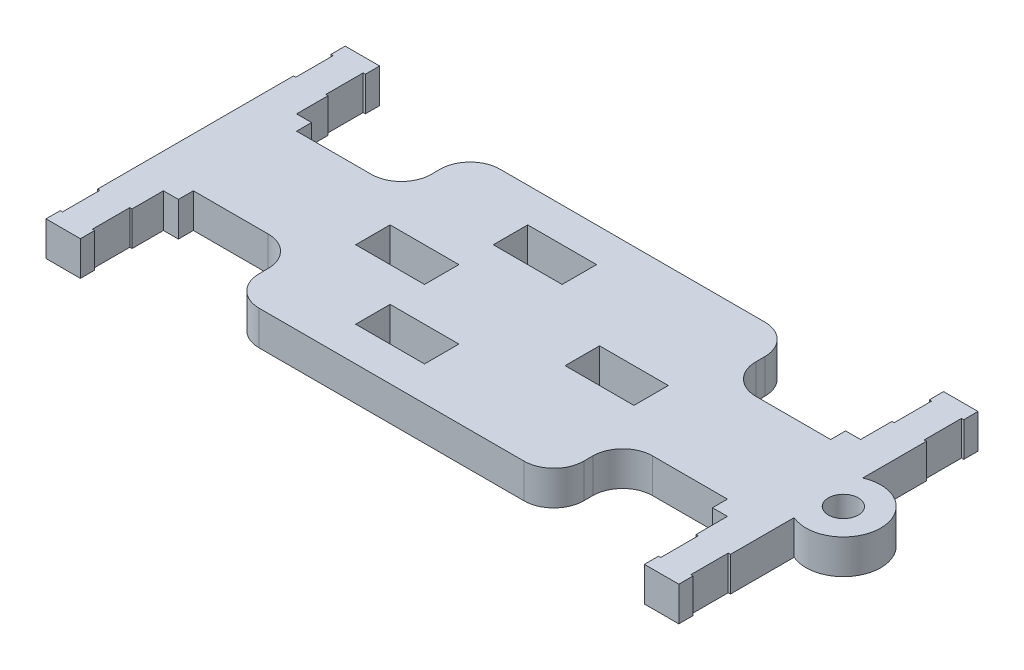
SolidWorks part; units mm, degrees
ref_plane "Front Plane" through (0, 0, 0) normal (0, 0, 1) x (1, 0, 0)
ref_plane "Top Plane" through (0, 0, 0) normal (0, 1, 0) x (1, 0, 0)
ref_plane "Right Plane" through (0, 0, 0) normal (1, 0, 0) x (0, 0, -1)
sketch "Sketch1" plane through (0, 0, 0) normal (0, 1, 0) x (1, 0, 0)
  line L0 (-15.3614, 0) -> (15.3614, 0) construction
  line L1 (-21.15, -10) -> (21.15, -10)
  line L2 (-21.15, -10) -> (-21.15, 10)
  line L3 (-21.15, 10) -> (21.15, 10)
  line L4 (21.15, -10) -> (21.15, 10)
  line L5 (-21.15, -10) -> (21.15, 10) construction
  line L6 (-21.15, 10) -> (21.15, -10) construction
  line L7 (-4.7, -1.15) -> (-9.3, -1.15)
  line L8 (-4.7, -1.15) -> (-4.7, 1.15)
  line L9 (-4.7, 1.15) -> (-9.3, 1.15)
  line L10 (-9.3, -1.15) -> (-9.3, 1.15)
  line L11 (-4.7, -1.15) -> (-9.3, 1.15) construction
  line L12 (-4.7, 1.15) -> (-9.3, -1.15) construction
  line L13 (-4.7, -3.45) -> (-0.1, -3.45)
  line L14 (-4.7, -3.45) -> (-4.7, -5.75)
  line L15 (-4.7, -5.75) -> (-0.1, -5.75)
  line L16 (-0.1, -3.45) -> (-0.1, -5.75)
  line L17 (0, -4.6731) -> (0, 4.6731) construction
  line L18 (9.3, -1.15) -> (9.3, 1.15)
  line L19 (4.7, 1.15) -> (9.3, 1.15)
  line L20 (4.7, -1.15) -> (9.3, -1.15)
  line L21 (4.7, -1.15) -> (4.7, 1.15)
  line L22 (-4.7, 5.75) -> (-0.1, 5.75)
  line L23 (-0.1, 3.45) -> (-0.1, 5.75)
  line L24 (-4.7, 3.45) -> (-0.1, 3.45)
  line L25 (-4.7, 3.45) -> (-4.7, 5.75)
  point P0 (0, 0)
  point P6 (-7, 0)
  point P19 (0, 0)
  point P21 (0, 0)
  dimension "D1" = 20
  dimension "D2" = 42.3
  dimension "D3" = 4.7
  dimension "D4" = 4.6
  dimension "D5" = 2.3
  dimension "D6" = 4.6
  dimension "D7" = 2.3
  dimension "D8" = 2.3
base flange "Base-Flange1" sketch "Sketch1" thickness 2.3 reverse thickness direction no parameters "D1"=0.7366
sketch "Sketch6" plane through (0, 0, 0) normal (0, 1, 0) x (1, 0, 0)
  line L0 (-2.4727, 0) -> (2.4727, 0) construction
  line L1 (-18.85, 10) -> (-18.85, 4.45)
  line L2 (21.15, 10) -> (-21.15, 10) construction
  line L3 (-17.85, 3.45) -> (-12.85, 3.45)
  line L4 (-10.85, 5.45) -> (-10.85, 6.05)
  line L5 (-8.85, 8.05) -> (8.85, 8.05)
  line L6 (10.85, 6.05) -> (10.85, 5.45)
  line L7 (12.85, 3.45) -> (17.85, 3.45)
  line L8 (18.85, 4.45) -> (18.85, 10)
  line L9 (18.85, 10) -> (-18.85, 10)
  line L10 (18.85, -10) -> (-18.85, -10)
  line L11 (18.85, -4.45) -> (18.85, -10)
  line L12 (12.85, -3.45) -> (17.85, -3.45)
  line L13 (10.85, -6.05) -> (10.85, -5.45)
  line L14 (-8.85, -8.05) -> (8.85, -8.05)
  line L15 (-10.85, -5.45) -> (-10.85, -6.05)
  line L16 (-17.85, -3.45) -> (-12.85, -3.45)
  line L17 (-18.85, -10) -> (-18.85, -4.45)
  line L18 (-18.85, 4.45) -> (-17.85, 4.45)
  line L19 (-17.85, 4.45) -> (-17.85, 3.45)
  line L20 (18.85, 4.45) -> (17.85, 4.45)
  line L21 (17.85, 4.45) -> (17.85, 3.45)
  line L22 (17.85, -3.45) -> (17.85, -4.45)
  line L23 (17.85, -4.45) -> (18.85, -4.45)
  line L24 (-18.85, -4.45) -> (-17.85, -4.45)
  line L25 (-17.85, -4.45) -> (-17.85, -3.45)
  arc A0 (-12.85, 3.45) -> (-10.85, 5.45) centre (-12.85, 5.45) ccw
  arc A1 (10.85, 5.45) -> (12.85, 3.45) centre (12.85, 5.45) ccw
  arc A2 (8.85, 8.05) -> (10.85, 6.05) centre (8.85, 6.05) cw
  arc A3 (-10.85, 6.05) -> (-8.85, 8.05) centre (-8.85, 6.05) cw
  arc A8 (-10.85, -6.05) -> (-8.85, -8.05) centre (-8.85, -6.05) ccw
  arc A9 (8.85, -8.05) -> (10.85, -6.05) centre (8.85, -6.05) ccw
  arc A10 (10.85, -5.45) -> (12.85, -3.45) centre (12.85, -5.45) cw
  arc A11 (-12.85, -3.45) -> (-10.85, -5.45) centre (-12.85, -5.45) cw
  point P4 (0, 0)
  point P20 (-10.85, 3.45)
  point P23 (10.85, 3.45)
  point P32 (-18.85, 3.45)
  point P53 (-18.85, -3.45)
  point P54 (10.85, -3.45)
  point P55 (-10.85, -3.45)
  dimension "D7" = 2
  dimension "D8" = 1
  dimension "D1" = 2.3
  dimension "D2" = 2.3
  dimension "D3" = 2.3
  dimension "D4" = 3.45
  dimension "D5" = 8
  dimension "D6" = 1.95
extrude "Cut-Extrude1" cut sketch "Sketch6" against normal up to next normal cut yes
sketch "Sketch7" plane through (0, 0, 0) normal (0, 1, 0) x (1, 0, 0)
  line L0 (-20, 10) -> (-20, 12.6051) construction
  line L1 (-21, 9.05) -> (-21, 6.55)
  line L2 (-18.85, 10) -> (-18.85, 4.45) construction
  line L3 (-21.15, 6.55) -> (-21, 6.55)
  line L4 (-18.85, 9.05) -> (-19, 9.05)
  line L5 (-21.15, 9.05) -> (-21.15, 6.55)
  line L6 (-18.85, 9.05) -> (-18.85, 6.55)
  line L7 (-18.85, 6.55) -> (-19, 6.55)
  line L8 (-19, 9.05) -> (-19, 6.55)
  line L9 (-21.15, 9.05) -> (-21, 9.05)
  line L10 (-3.5932, 0) -> (3.5932, 0) construction
  line L11 (0, -2.3278) -> (0, 2.3278) construction
  line L12 (-21.15, -9.05) -> (-21, -9.05)
  line L13 (-19, -9.05) -> (-19, -6.55)
  line L14 (-18.85, -6.55) -> (-19, -6.55)
  line L15 (-18.85, -9.05) -> (-18.85, -6.55)
  line L16 (-21.15, -9.05) -> (-21.15, -6.55)
  line L17 (-18.85, -9.05) -> (-19, -9.05)
  line L18 (-21.15, -6.55) -> (-21, -6.55)
  line L19 (-21, -9.05) -> (-21, -6.55)
  line L20 (21, -9.05) -> (21, -6.55)
  line L21 (21.15, -6.55) -> (21, -6.55)
  line L22 (18.85, -9.05) -> (19, -9.05)
  line L23 (21.15, -9.05) -> (21.15, -6.55)
  line L24 (18.85, -9.05) -> (18.85, -6.55)
  line L25 (18.85, -6.55) -> (19, -6.55)
  line L26 (19, -9.05) -> (19, -6.55)
  line L27 (21.15, -9.05) -> (21, -9.05)
  line L28 (21.15, 9.05) -> (21, 9.05)
  line L29 (19, 9.05) -> (19, 6.55)
  line L30 (18.85, 6.55) -> (19, 6.55)
  line L31 (18.85, 9.05) -> (18.85, 6.55)
  line L32 (21.15, 9.05) -> (21.15, 6.55)
  line L33 (18.85, 9.05) -> (19, 9.05)
  line L34 (21.15, 6.55) -> (21, 6.55)
  line L35 (21, 9.05) -> (21, 6.55)
  point P18 (0, 0)
  point P22 (0, 0)
  dimension "D1" = 0.15
  dimension "D2" = 2.5
  dimension "D3" = 2.1
  dimension "D4" = 0.95
extrude "Cut-Extrude2" cut sketch "Sketch7" against normal up to next normal cut yes
sketch "Sketch8" plane through (0, 0, 0) normal (0, 1, 0) x (1, 0, 0)
  circle A1 centre (22.15, 0) radius 1
  circle A2 centre (22.15, 0) radius 2.5
  dimension "D1" = 5
  dimension "D2" = 2
base flange "Tab1" sketch "Sketch8" thickness 2.3 reverse thickness direction no parameters "D1"=0.7366
sketch "Bend-Lines1" [suppressed] plane through (0, 0, 0) normal (0, 1, 0) x (1, 0, 0)
sketch "Bounding-Box1" [suppressed] plane through (0, 0, 0) normal (0, 1, 0) x (1, 0, 0)
sheet metal parameters "Sheet-Metal1" thickness 2.3 parameters "D1"=0.7366
flat pattern "Flat-Pattern1" [suppressed]
sketch "Bend-Lines2" plane through (0, 0, 0) normal (0, 1, 0) x (1, 0, 0)
sketch3d "Bounding-Box2" [suppressed]
  line L0 (-21.15, 10, 0) -> (21.15, 10, 0) construction
  line L1 (-21.15, -10, 0) -> (21.15, -10, 0) construction
  line L2 (-21.15, 10, 0) -> (-21.15, -10, 0) construction
  line L3 (21.15, 10, 0) -> (21.15, -10, 0) construction
sheet metal parameters "Sheet-Metal2" thickness 2.3 parameters "D1"=0.7366
flat pattern "Flat-Pattern1"
sketch "Bend-Lines2" plane through (0, 0, 0) normal (0, 1, 0) x (1, 0, 0)
sketch3d "Bounding-Box2" [suppressed]
  line L0 (21.15, 10, 0) -> (-21.15, 10, 0) construction
  line L1 (21.15, -10, 0) -> (-21.15, -10, 0) construction
  line L2 (21.15, 10, 0) -> (21.15, -10, 0) construction
  line L3 (-21.15, 10, 0) -> (-21.15, -10, 0) construction
sheet metal parameters "Sheet-Metal3" thickness 2.3 parameters "D1"=0.7366
flat pattern "Flat-Pattern1"
sketch "Bend-Lines2" plane through (0, 0, 0) normal (0, 1, 0) x (1, 0, 0)
sketch3d "Bounding-Box2" [suppressed]
  line L0 (21.15, 10, 0) -> (-21.15, 10, 0) construction
  line L1 (21.15, -10, 0) -> (-21.15, -10, 0) construction
  line L2 (21.15, 10, 0) -> (21.15, -10, 0) construction
  line L3 (-21.15, 10, 0) -> (-21.15, -10, 0) construction
sheet metal parameters "Sheet-Metal4" thickness 2.3 parameters "D1"=0.7366
flat pattern "Flat-Pattern4"
sketch "Bend-Lines3" plane through (0, 0, 0) normal (0, 1, 0) x (1, 0, 0)
sketch3d "Bounding-Box3" [suppressed]
  line L0 (24.6496, 10, 0) -> (-21.15, 10, 0) construction
  line L1 (24.6496, -10, 0) -> (-21.15, -10, 0) construction
  line L2 (24.6496, 10, 0) -> (24.6496, -10, 0) construction
  line L3 (-21.15, 10, 0) -> (-21.15, -10, 0) construction
